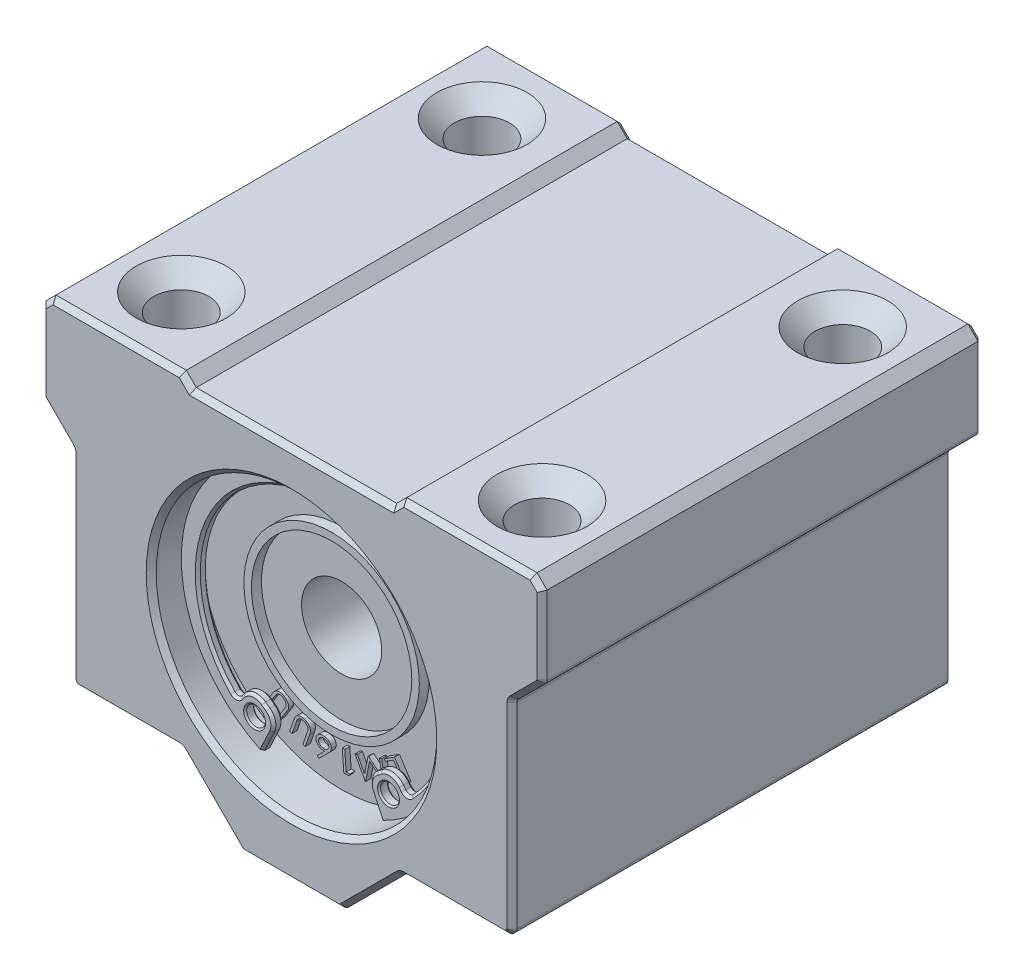
SolidWorks part; units mm, degrees
other "Camera1"
ref_plane "Front Plane" through (0, 0, 0) normal (0, 0, 1) x (1, 0, 0)
ref_plane "Top Plane" through (0, 0, 0) normal (0, 1, 0) x (1, 0, 0)
ref_plane "Right Plane" through (0, 0, 0) normal (1, 0, 0) x (0, 0, -1)
sketch "Sketch1" plane through (0, 0, 0) normal (0, 0, 1) x (1, 0, 0)
  line L0 (0, 67.7363) -> (0, -68.8522) construction
  line L1 (-82.02, 0) -> (119.5149, 0) construction
  line L2 (-24, 22.949) -> (-11, 22.949)
  line L3 (-25, 21.949) -> (-25, 14.1561)
  line L4 (24.8536, 13.8025) -> (22.1464, 11.0954)
  line L5 (-22, 10.7419) -> (-22, -8.8439)
  line L6 (-11.2071, -9.551) -> (-21.2929, -9.551)
  line L7 (-24.8536, 13.8025) -> (-22.1464, 11.0954)
  line L8 (4.7929, -15.551) -> (-4.7929, -15.551)
  line L9 (5.1464, -15.4046) -> (10.8536, -9.6975)
  line L10 (11.2071, -9.551) -> (21.2929, -9.551)
  line L11 (22, 10.7419) -> (22, -8.8439)
  line L12 (0, 21.949) -> (-10, 21.949)
  line L13 (25, 21.949) -> (25, 14.1561)
  line L14 (-5.1464, -15.4046) -> (-10.8536, -9.6975)
  line L15 (-10, 21.949) -> (-11, 22.949)
  line L16 (10, 21.949) -> (11, 22.949)
  line L17 (24, 22.949) -> (11, 22.949)
  line L18 (0, 21.949) -> (10, 21.949)
  line L19 (-25, 21.949) -> (-24, 22.949)
  line L20 (25, 21.949) -> (24, 22.949)
  line L21 (-21.8536, -9.1975) -> (-21.6464, -9.4046)
  line L22 (21.6464, -9.4046) -> (21.8536, -9.1975)
  arc A0 (-25, 14.1561) -> (-24.8536, 13.8025) centre (-24.5, 14.1561) ccw
  arc A1 (25, 14.1561) -> (24.8536, 13.8025) centre (24.5, 14.1561) cw
  arc A2 (22.1464, 11.0954) -> (22, 10.7419) centre (22.5, 10.7419) ccw
  arc A3 (-22, 10.7419) -> (-22.1464, 11.0954) centre (-22.5, 10.7419) ccw
  arc A4 (21.8536, -9.1975) -> (22, -8.8439) centre (21.5, -8.8439) ccw
  arc A5 (21.6464, -9.4046) -> (21.2929, -9.551) centre (21.2929, -9.051) cw
  arc A6 (-21.2929, -9.551) -> (-21.6464, -9.4046) centre (-21.2929, -9.051) cw
  arc A7 (-22, -8.8439) -> (-21.8536, -9.1975) centre (-21.5, -8.8439) ccw
  arc A8 (11.2071, -9.551) -> (10.8536, -9.6975) centre (11.2071, -10.051) ccw
  arc A9 (-10.8536, -9.6975) -> (-11.2071, -9.551) centre (-11.2071, -10.051) ccw
  arc A10 (4.7929, -15.551) -> (5.1464, -15.4046) centre (4.7929, -15.051) ccw
  arc A11 (-4.7929, -15.551) -> (-5.1464, -15.4046) centre (-4.7929, -15.051) cw
  circle A12 centre (0, 3.949) radius 14
  point P10 (-22, -9.551)
  point P15 (22, -9.551)
  point P30 (-25, 13.949)
  point P33 (25, 13.949)
  point P38 (-22, 10.949)
  point P41 (22, -9.051)
  point P44 (21.5, -9.551)
  point P47 (-21.5, -9.551)
  point P50 (-22, -9.051)
  point P57 (5, -15.551)
  point P60 (-5, -15.551)
  dimension "D16" = 0.5
  dimension "D18" = 28
  dimension "D1" = 50
  dimension "D2" = 20.5
  dimension "D3" = 32.5
  dimension "D4" = 38.5
  dimension "D5" = 3
  dimension "D6" = 10
  dimension "D7" = 135
  dimension "D8" = 135
  dimension "D9" = 135
  dimension "D10" = 135
  dimension "D11" = 1
  dimension "D12" = 1
  dimension "D13" = 1
  dimension "D14" = 1
  dimension "D15" = 1
  dimension "D17" = 19
  dimension "D21" = 13
extrude "Boss-Extrude1" add sketch "Sketch1" along normal mid plane 44
sketch "Sketch2" plane through (0, 0, 0) normal (0, 0, 1) x (1, 0, 0)
  circle A0 centre (0, 3.949) radius 4
  circle A1 centre (0, 3.949) radius 14
  dimension "D1" = 8
extrude "Boss-Extrude2" add sketch "Sketch2" along normal mid plane 34
sketch "Sketch3" plane through (0, 0, 17) normal (0, 0, 1) x (1, 0, 0)
  circle A0 centre (0, 3.949) radius 8
  circle A1 centre (0, 3.949) radius 8.75
  dimension "D1" = 0.75
extrude "Boss-Extrude3" add sketch "Sketch3" along normal blind 1 separate body
sketch "Sketch4" plane through (0, 0, -17) normal (0, 0, -1) x (-1, 0, 0)
  circle A0 centre (0, 3.949) radius 8
  circle A1 centre (0, 3.949) radius 8.75
  dimension "D1" = 0.75
extrude "Boss-Extrude4" add sketch "Sketch4" along normal blind 1
ref_plane "Plane1" through (0, 0, 18) normal (0, 0, 1) x (1, 0, 0)
sketch "Sketch5" plane through (0, 0, 18) normal (0, 0, 1) x (1, 0, 0)
  line L0 (0, -16.8166) -> (0, 25.4288) construction
  line L1 (0, 3.949) -> (-8.9403, -15.2235) construction
  line L2 (0, 3.949) -> (10.438, -18.4353) construction
  line L3 (5.9167, -8.7393) -> (4.9498, -6.6658)
  line L4 (5.4106, -4.8309) -> (5.8303, -4.5168)
  line L5 (7.93, -4.8192) -> (8.1411, -5.1014)
  line L6 (-7.93, -4.8192) -> (-8.1411, -5.1014)
  line L7 (-5.4106, -4.8309) -> (-5.8303, -4.5168)
  line L8 (-4.9498, -6.6658) -> (-5.9167, -8.7393)
  line L9 (5.4793, -4.4853) -> (7.5685, -7.2774) construction
  arc A0 (5.9167, -8.7393) -> (-5.9167, -8.7393) centre (0, 3.949) ccw
  arc A1 (5.8303, -4.5168) -> (7.93, -4.8192) centre (6.729, -5.7178) cw
  arc A2 (5.4106, -4.8309) -> (4.9498, -6.6658) centre (6.3092, -6.0319) ccw
  arc A3 (-5.4106, -4.8309) -> (-4.9498, -6.6658) centre (-6.3092, -6.0319) cw
  arc A4 (-5.8303, -4.5168) -> (-7.93, -4.8192) centre (-6.729, -5.7178) ccw
  arc A5 (8.9016, -5.1487) -> (-8.9016, -5.1487) centre (0, 3.4237) ccw
  arc A6 (8.1411, -5.1014) -> (8.9016, -5.1487) centre (8.5415, -4.8018) ccw
  arc A7 (-8.9016, -5.1487) -> (-8.1411, -5.1014) centre (-8.5415, -4.8018) ccw
  circle A8 centre (6.685, -6.0966) radius 0.9432
  circle A9 centre (-6.685, -6.0966) radius 0.9432
  point P16 (4.4346, -5.5611)
  point P27 (8.4851, -5.5611)
  point P30 (-8.4851, -5.5611)
  dimension "D3" = 1.5
  dimension "D4" = 0.5
  dimension "D5" = 0.5
  dimension "D1" = 25
  dimension "D2" = 25
extrude "Boss-Extrude5" add sketch "Sketch5" along normal blind 1
ref_plane "Plane2" through (0, 0, -18) normal (0, 0, -1) x (-1, 0, 0)
sketch "Sketch6" plane through (0, 0, -18) normal (0, 0, -1) x (-1, 0, 0)
  line L0 (0, -16.8166) -> (0, 25.4288) construction
  line L1 (0, 3.949) -> (-8.9403, -15.2235) construction
  line L2 (0, 3.949) -> (10.438, -18.4353) construction
  line L3 (5.9167, -8.7393) -> (4.9498, -6.6658)
  line L4 (5.4106, -4.8309) -> (5.8303, -4.5168)
  line L5 (7.93, -4.8192) -> (8.1411, -5.1014)
  line L6 (-7.93, -4.8192) -> (-8.1411, -5.1014)
  line L7 (-5.4106, -4.8309) -> (-5.8303, -4.5168)
  line L8 (-4.9498, -6.6658) -> (-5.9167, -8.7393)
  line L9 (5.4793, -4.4853) -> (7.5685, -7.2774) construction
  line L10 (0, 11.949) -> (0, -6.6658) construction
  line L11 (9.5261, 3.949) -> (-9.8165, 3.949) construction
  arc A0 (5.9167, -8.7393) -> (-5.9167, -8.7393) centre (0, 3.949) ccw
  arc A1 (5.8303, -4.5168) -> (7.93, -4.8192) centre (6.729, -5.7178) cw
  arc A2 (5.4106, -4.8309) -> (4.9498, -6.6658) centre (6.3092, -6.0319) ccw
  arc A3 (-5.4106, -4.8309) -> (-4.9498, -6.6658) centre (-6.3092, -6.0319) cw
  arc A4 (-5.8303, -4.5168) -> (-7.93, -4.8192) centre (-6.729, -5.7178) ccw
  arc A5 (8.9016, -5.1487) -> (-8.9016, -5.1487) centre (0, 3.4237) ccw
  arc A6 (8.1411, -5.1014) -> (8.9016, -5.1487) centre (8.5415, -4.8018) ccw
  arc A7 (-8.9016, -5.1487) -> (-8.1411, -5.1014) centre (-8.5415, -4.8018) ccw
  circle A8 centre (6.685, -6.0966) radius 0.9432
  circle A9 centre (-6.685, -6.0966) radius 0.9432
  circle A10 centre (0, 3.949) radius 8 construction
  dimension "D3" = 1.5
  dimension "D4" = 0.5
  dimension "D5" = 0.5
  dimension "D1" = 25
  dimension "D2" = 25
extrude "Boss-Extrude6" add sketch "Sketch6" along normal blind 1
sketch "Sketch7" plane through (0, 0, 17) normal (0, 0, 1) x (1, 0, 0)
  arc A0 (6.0248, -3.9414) -> (-6.0089, -3.9536) centre (0, 3.949) cw construction
  text T0 "LM16UU" font "Century Gothic" height in points 8
extrude "Boss-Extrude7" add sketch "Sketch7" along normal blind 0.5 separate body
chamfer "Chamfer1" distance 0.5 angle 45 64 edges at (17.5, 22.949, 22) (10.5, 22.449, 22) (0, 21.949, 22) (10.5, 22.449, -22) (0, 21.949, -22) (-10.5, 22.449, -22) (-17.5, 22.949, -22) (-24.5, 22.449, -22) (-25, 18.0525, -22) (-24.9619, 13.9647, -22) (-23.5, 12.449, -22) (-22.0381, 10.9332, -22) (-22, 0.949, -22) (-21.9619, -9.0353, -22) (-21.75, -9.301, -22) (-21.4842, -9.513, -22) (-16.25, -9.551, -22) (-11.0158, -9.5891, -22) (-8, -12.551, -22) (-4.9842, -15.513, -22) (0, -15.551, -22) (4.9842, -15.513, -22) (8, -12.551, -22) (11.0158, -9.5891, -22) (16.25, -9.551, -22) (21.4842, -9.513, -22) (21.75, -9.301, -22) (21.9619, -9.0353, -22) (22, 0.949, -22) (22.0381, 10.9332, -22) (23.5, 12.449, -22) (24.9619, 13.9647, -22) (17.5, 22.949, -22) (25, 18.0525, -22) (24.5, 22.449, -22) (-10.5, 22.449, 22) (-17.5, 22.949, 22) (-24.5, 22.449, 22) (-25, 18.0525, 22) (-24.9619, 13.9647, 22) (-23.5, 12.449, 22) (-22.0381, 10.9332, 22) (-22, 0.949, 22) (-21.9619, -9.0353, 22) (-21.75, -9.301, 22) (-21.4842, -9.513, 22) (-16.25, -9.551, 22) (-11.0158, -9.5891, 22) (-8, -12.551, 22) (-4.9842, -15.513, 22) (0, -15.551, 22) (4.9842, -15.513, 22) (8, -12.551, 22) (11.0158, -9.5891, 22) (16.25, -9.551, 22) (21.4842, -9.513, 22) (21.75, -9.301, 22) (21.9619, -9.0353, 22) (22, 0.949, 22) (22.0381, 10.9332, 22) (23.5, 12.449, 22) (24.9619, 13.9647, 22) (25, 18.0525, 22) (24.5, 22.449, 22)
chamfer "Chamfer2" distance 0.5 angle 45 2 edges at (14, 3.949, 22) (14, 3.949, -22)
chamfer "Chamfer3" distance 0.25 angle 45 52 edges at (5.4332, -7.7026, -18) (-5.4332, -7.7026, -18) (4.8544, -5.6665, -18) (-4.8544, -5.6665, -18) (5.6204, -4.6739, -18) (-5.6204, -4.6739, -18) (6.9428, -4.2331, -18) (-6.9428, -4.2331, -18) (8.0355, -4.9603, -18) (-8.0355, -4.9603, -18) (8.5104, -5.3009, -18) (-8.5104, -5.3009, -18) (0, 15.7819, -18) (5.4332, -7.7026, -19) (-5.4332, -7.7026, -19) (4.8544, -5.6665, -19) (-4.8544, -5.6665, -19) (5.6204, -4.6739, -19) (-5.6204, -4.6739, -19) (6.9428, -4.2331, -19) (-6.9428, -4.2331, -19) (8.0355, -4.9603, -19) (-8.0355, -4.9603, -19) (8.5104, -5.3009, -19) (-8.5104, -5.3009, -19) (0, 15.7819, -19) (-5.4332, -7.7026, 18) (5.4332, -7.7026, 18) (-4.8544, -5.6665, 18) (4.8544, -5.6665, 18) (-5.6204, -4.6739, 18) (5.6204, -4.6739, 18) (-6.9428, -4.2331, 18) (6.9428, -4.2331, 18) (-8.0355, -4.9603, 18) (8.0355, -4.9603, 18) (-8.5104, -5.3009, 18) (8.5104, -5.3009, 18) (0, 15.7819, 18) (-5.4332, -7.7026, 19) (5.4332, -7.7026, 19) (-4.8544, -5.6665, 19) (4.8544, -5.6665, 19) (-5.6204, -4.6739, 19) (5.6204, -4.6739, 19) (-6.9428, -4.2331, 19) (6.9428, -4.2331, 19) (-8.0355, -4.9603, 19) (8.0355, -4.9603, 19) (-8.5104, -5.3009, 19) (8.5104, -5.3009, 19) (0, 15.7819, 19)
chamfer "Chamfer4" distance 0.15 angle 45 8 edges at (7.6282, -6.0966, 19) (7.6282, -6.0966, 18) (7.6282, -6.0966, -19) (7.6282, -6.0966, -18) (-7.6282, -6.0966, -18) (-7.6282, -6.0966, -19) (-7.6282, -6.0966, 18) (-7.6282, -6.0966, 19)
hole_wizard "CSK for M5 Countersunk Flat Head Screw1" positions "3DSketch1" profile "Sketch9" countersink size "M5" standard "DIN"
sketch3d "3DSketch1"
  point P0 (18, 22.949, 15)
  point P2 (-18, 22.949, 15)
  point P4 (-18, 22.949, -15)
  point P6 (18, 22.949, -15)
  dimension "D1" = 7
  dimension "D2" = 7
  dimension "D3" = 7
  dimension "D4" = 7
  dimension "D5" = 7
  dimension "D6" = 7
  dimension "D7" = 7
  dimension "D8" = 7
sketch "Sketch9" plane through (18, 22.949, 15) normal (1, 0, 0) x (0, 0, 1)
  line L0 (0, 0) -> (0, 13.6524)
  line L1 (0, 13.6524) -> (2.75, 12)
  line L2 (2.75, 12) -> (2.75, 1.75)
  line L3 (2.75, 1.75) -> (4.5, 0)
  line L5 (4.5, 0) -> (0, 0)
  line L6 (-2.75, 1.75) -> (-4.5, 0) construction
  line L10 (0, 13.6524) -> (-2.75, 12) construction
  line L11 (0, -6.35) -> (0, 107.95) construction
  dimension "Hole Dia." = 5.5
  dimension "Hole Depth" = 12
  dimension "Near C'Sink Dia." = 9
  dimension "Near C'Sink Angle" = 90
  dimension "Drill Angle" = 118
hole_wizard "CSK for M4 Countersunk Flat Head Screw1" positions "3DSketch2" profile "Sketch10" countersink size "M4" standard "DIN"
sketch3d "3DSketch2"
  point P0 (-17, -9.551, 17)
  point P2 (-17, -9.551, -17)
  point P4 (17, -9.551, -17)
  point P6 (17, -9.551, 17)
  dimension "D1" = 5
  dimension "D2" = 5
  dimension "D3" = 5
  dimension "D4" = 5
  dimension "D5" = 5
  dimension "D6" = 5
  dimension "D7" = 5
  dimension "D8" = 5
sketch "Sketch10" plane through (-17, -9.551, 17) normal (1, 0, 0) x (0, 0, -1)
  line L0 (0, 0) -> (0, 13.2919)
  line L1 (0, 13.2919) -> (2.15, 12)
  line L2 (2.15, 12) -> (2.15, 1.35)
  line L3 (2.15, 1.35) -> (3.5, 0)
  line L5 (3.5, 0) -> (0, 0)
  line L6 (-2.15, 1.35) -> (-3.5, 0) construction
  line L10 (0, 13.2919) -> (-2.15, 12) construction
  line L11 (0, -6.35) -> (0, 107.95) construction
  dimension "Hole Dia." = 4.3
  dimension "Hole Depth" = 12
  dimension "Near C'Sink Dia." = 7
  dimension "Near C'Sink Angle" = 90
  dimension "Drill Angle" = 118
